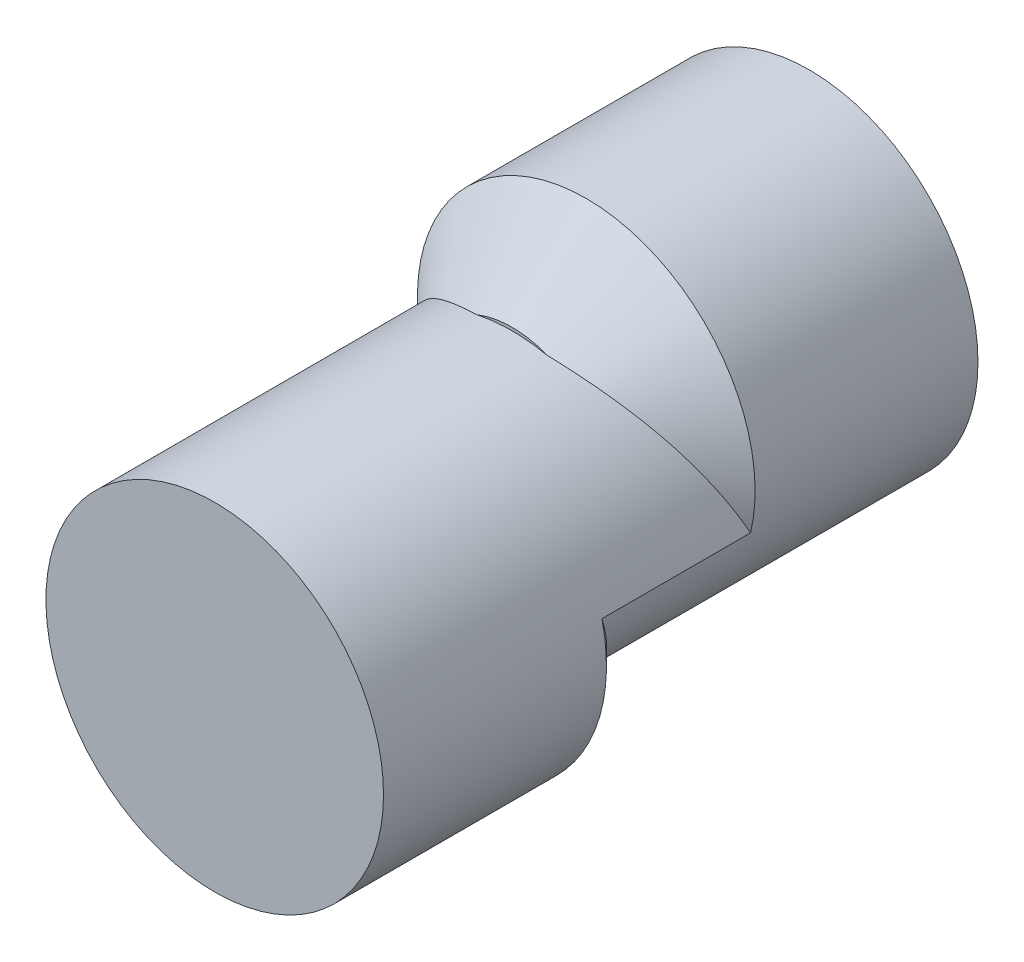
SolidWorks part; units mm, degrees
ref_plane "Plan de face" through (0, 0, 0) normal (0, 0, 1) x (1, 0, 0)
ref_plane "Plan de dessus" through (0, 0, 0) normal (0, 1, 0) x (1, 0, 0)
ref_plane "Plan de droite" through (0, 0, 0) normal (1, 0, 0) x (0, 0, -1)
sketch "Esquisse1" plane through (0, 0, 0) normal (0, 0, 1) x (1, 0, 0)
  circle A1 centre (0, 0.8221) radius 3.975
  dimension "D3" = 7.95
extrude "Boss.-Extru.1" add sketch "Esquisse1" along normal blind 7
sketch "Esquisse2" plane through (0, 0, 7) normal (0, 0, 1) x (1, 0, 0)
  circle A0 centre (0, -1) radius 3.975
  dimension "D1" = 7.95
  dimension "D2" = 1
extrude "Boss.-Extru.2" add sketch "Esquisse2" along normal blind 7
sketch "Esquisse3" plane through (0, 0, 14) normal (0, 0, 1) x (1, 0, 0)
  line L0 (-1.5, 2) -> (1.5, 2) construction
  line L1 (-1.533, 2.1) -> (1.533, 2.1)
  arc A0 (-1.5, 2) -> (1.5, 2) centre (0, 0) ccw construction
  arc A1 (-1.533, 2.1) -> (1.533, 2.1) centre (0, 0) ccw
  dimension "D1" = 5
  dimension "D2" = 2
  dimension "D3" = 0.1
extrude "Enlèv. mat.-Extru.1" cut sketch "Esquisse3" against normal through all from offset 2 offset against normal yes
chamfer "Chanfrein2" distance 1.75 angle 45 1 edges at (0, 4.7971, 7)
chamfer "Chanfrein4" distance 1.75 angle 45 1 edges at (0, -4.975, 7)
